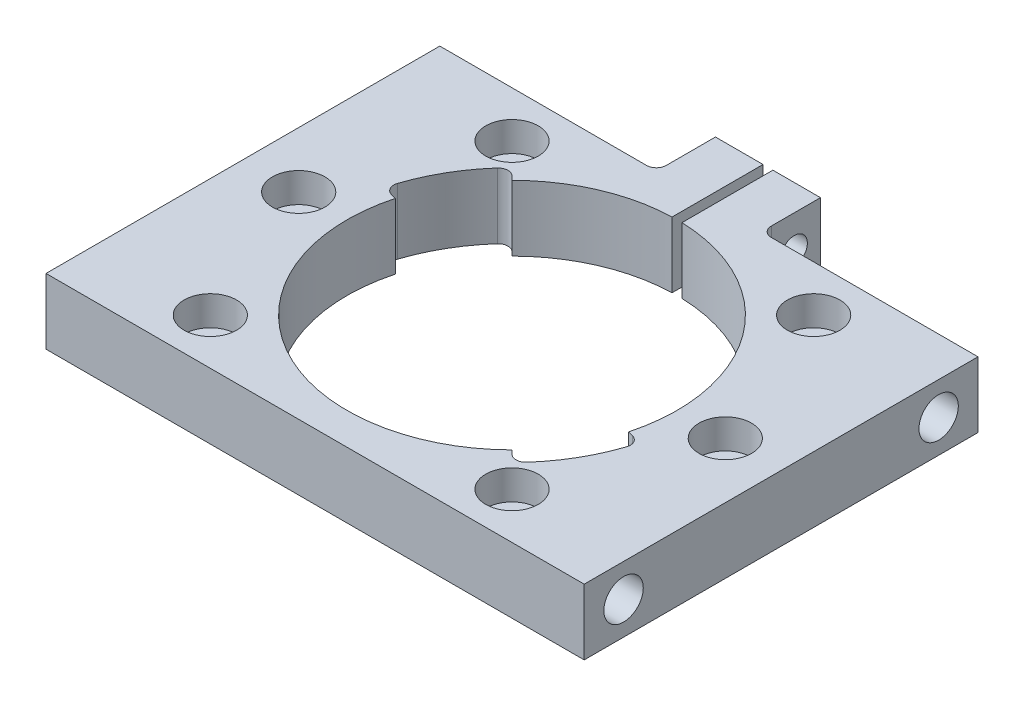
SolidWorks part; units mm, degrees
material "6061 Alloy"
ref_plane "Front Plane" through (0, 0, 0) normal (0, 0, 1) x (1, 0, 0)
ref_plane "Top Plane" through (0, 0, 0) normal (0, 1, 0) x (1, 0, 0)
ref_plane "Right Plane" through (0, 0, 0) normal (1, 0, 0) x (0, 0, -1)
sketch "Sketch1" plane through (0, 76, 0) normal (0, 1, 0) x (1, 0, 0)
  line L0 (-18.3542, 18.3542) -> (18.3542, -18.3542)
  line L1 (-41, -30) -> (41, -30)
  line L2 (-41, -30) -> (-41, 30)
  line L3 (-41, 30) -> (41, 30)
  line L4 (41, -30) -> (41, 30)
  line L5 (-41, -30) -> (41, 30) construction
  line L6 (-41, 30) -> (41, -30) construction
  line L7 (-25.0722, 6.7181) -> (25.0722, -6.7181)
  line L8 (-103.759, 0) -> (103.759, 0) construction
  circle A0 centre (0, 0) radius 25.15
  arc A1 (-20.5349, 18.2912) -> (-26.1081, 8.6381) centre (0, 0) ccw
  arc A2 (26.1081, -8.6381) -> (20.5349, -18.2912) centre (0, 0) cw
  circle A3 centre (0, 0) radius 27.5 construction
  arc A4 (18.3542, -18.3542) -> (20.5349, -18.2912) centre (19.4148, -17.2935) ccw
  arc A5 (25.0722, -6.7181) -> (26.1081, -8.6381) centre (24.684, -8.167) cw
  arc A6 (-25.0722, 6.7181) -> (-26.1081, 8.6381) centre (-24.684, 8.167) cw
  arc A7 (-18.3542, 18.3542) -> (-20.5349, 18.2912) centre (-19.4148, 17.2935) ccw
  circle A8 centre (22.981, 22.981) radius 2 construction
  circle A9 centre (32.5, 0) radius 2 construction
  circle A10 centre (22.981, -22.981) radius 2 construction
  circle A11 centre (-22.981, -22.981) radius 2 construction
  circle A12 centre (-32.5, 0) radius 2 construction
  circle A13 centre (-22.981, 22.981) radius 2 construction
  circle A14 centre (22.981, 22.981) radius 2
  circle A15 centre (32.5, 0) radius 2
  circle A16 centre (22.981, -22.981) radius 2
  circle A17 centre (-22.981, -22.981) radius 2
  circle A18 centre (-32.5, 0) radius 2
  circle A19 centre (-22.981, 22.981) radius 2
  point P0 (0, 0)
  dimension "D1" = 50.3
  dimension "D4" = 1.5
  dimension "D2" = 45
  dimension "D3" = 15
  dimension "D5" = 82
  dimension "D6" = 60
extrude "Boss-Extrude1" add sketch "Sketch1" along normal blind 10 contours L1 L4 L3 L2 A19 A18 A17 A16 A15 A14 A7 L0 A0 L7 A5 A2 A4 A6 A1 region at (-39.9839, 76, 0)
sketch "Sketch2" plane through (0, 86, 0) normal (0, 1, 0) x (1, 0, 0)
  line L0 (0, -142.3844) -> (0, 142.3844) construction
  line L1 (-8, 39) -> (8, 39)
  line L2 (-8, 39) -> (-8, 30)
  line L3 (-8, 30) -> (8, 30)
  line L4 (8, 39) -> (8, 30)
  line L5 (-8, 39) -> (8, 30) construction
  line L6 (-8, 30) -> (8, 39) construction
  line L7 (-41, 30) -> (41, 30) construction
  point P0 (0, 34.5)
  dimension "D1" = 9
  dimension "D2" = 16
extrude "Boss-Extrude2" add sketch "Sketch2" against normal blind 10
sketch "Sketch3" plane through (0, 86, 0) normal (0, 1, 0) x (1, 0, 0)
  line L0 (0, -142.3844) -> (0, 142.3844) construction
  line L1 (-0.75, 25) -> (0.75, 25)
  line L2 (-0.75, 25) -> (-0.75, 39)
  line L3 (-0.75, 39) -> (0.75, 39)
  line L4 (0.75, 25) -> (0.75, 39)
  line L5 (-0.75, 25) -> (0.75, 39) construction
  line L6 (-0.75, 39) -> (0.75, 25) construction
  line L7 (8, 39) -> (-8, 39) construction
  point P0 (0, 32)
  dimension "D1" = 14
  dimension "D2" = 1.5
extrude "Cut-Extrude1" cut sketch "Sketch3" against normal blind 10
sketch "Sketch4" plane through (8, 0, 0) normal (1, 0, 0) x (0, 0, -1)
  line L0 (35, 81) -> (39, 81) construction
  line L1 (39, 76) -> (39, 86) construction
  circle A0 centre (35, 81) radius 2
  dimension "D1" = 4
  dimension "D2" = 4
extrude "Cut-Extrude2" cut sketch "Sketch4" against normal up to vertex (7.25 mm away) up to point (0.75, 86, -39)
sketch "Sketch5" plane through (-0.75, 0, 0) normal (1, 0, 0) x (0, 0, -1)
  circle A0 centre (35, 81) radius 1.6
  dimension "D1" = 3.2
extrude "Cut-Extrude3" cut sketch "Sketch5" against normal blind 10
sketch "Sketch7" plane through (0, 86, 0) normal (0, 1, 0) x (1, 0, 0)
  circle A0 centre (-22.981, 22.981) radius 4
  circle A1 centre (22.981, 22.981) radius 4
  circle A2 centre (32.5, 0) radius 4
  circle A3 centre (-32.5, 0) radius 4
  circle A4 centre (-22.981, -22.981) radius 4
  circle A5 centre (22.981, -22.981) radius 4
  dimension "D1" = 8
extrude "Cut-Extrude4" cut sketch "Sketch7" against normal blind 4.5
fillet "Fillet1" radius 1.5 2 edges at (-8, 81, -30) (8, 81, -30)
sketch "Sketch8" plane through (0, 86, 0) normal (0, 1, 0) x (1, 0, 0)
  line L0 (9.4279, 0) -> (0, 0) construction
  line L1 (-41, 30) -> (-29, 30)
  line L2 (-41, 30) -> (-41, 18)
  line L3 (-41, 18) -> (-29, 18)
  line L4 (-29, 30) -> (-29, 18)
  line L5 (0, 0) -> (0, 11.3596) construction
  line L6 (29, 30) -> (29, 18)
  line L7 (41, 18) -> (29, 18)
  line L8 (41, 30) -> (41, 18)
  line L9 (41, 30) -> (29, 30)
  line L10 (41, -30) -> (29, -30)
  line L11 (41, -30) -> (41, -18)
  line L12 (41, -18) -> (29, -18)
  line L13 (29, -30) -> (29, -18)
  line L14 (-29, -30) -> (-29, -18)
  line L15 (-41, -18) -> (-29, -18)
  line L16 (-41, -30) -> (-41, -18)
  line L17 (-41, -30) -> (-29, -30)
  dimension "D1" = 12
  dimension "D2" = 12
extrude "Boss-Extrude3" add sketch "Sketch8" along normal blind 10
fillet "Fillet2" radius 1.5 8 edges at (35, 86, 18) (-35, 86, 18) (-29, 86, 24) (29, 86, 24) (29, 86, -24) (35, 86, -18) (-35, 86, -18) (-29, 86, -24)
sketch "Sketch9" plane through (-41, 0, 0) normal (-1, 0, 0) x (0, 0, 1)
  line L0 (0, 86) -> (0, 76) construction
  line L1 (16.5, 86) -> (-16.5, 86) construction
  line L2 (30, 76) -> (-30, 76) construction
  line L3 (-30, 96) -> (-18, 96) construction
  line L4 (-30, 96) -> (-30, 76) construction
  circle A0 centre (-24, 91) radius 3
  circle A1 centre (-24, 81) radius 3
  circle A2 centre (24, 81) radius 3
  circle A3 centre (24, 91) radius 3
  dimension "D2" = 6
  dimension "D3" = 6
  dimension "D4" = 5
  dimension "D5" = 6
  dimension "D1" = 5
extrude "Cut-Extrude5" cut sketch "Sketch9" against normal blind 12
mirror "Mirror1" about plane through (0, 0, 0) normal (1, 0, 0) of "Cut-Extrude5"
sketch "Sketch10" plane through (0, 86, 0) normal (0, 1, 0) x (1, 0, 0)
  line L1 (-41, 30) -> (41, 30)
  line L2 (-41, 30) -> (-41, -30)
  line L3 (-41, -30) -> (41, -30)
  line L4 (41, 30) -> (41, -30)
extrude "Cut-Extrude6" cut sketch "Sketch10" along normal up to vertex (10 mm away) up to point (-41, 96, -30)
